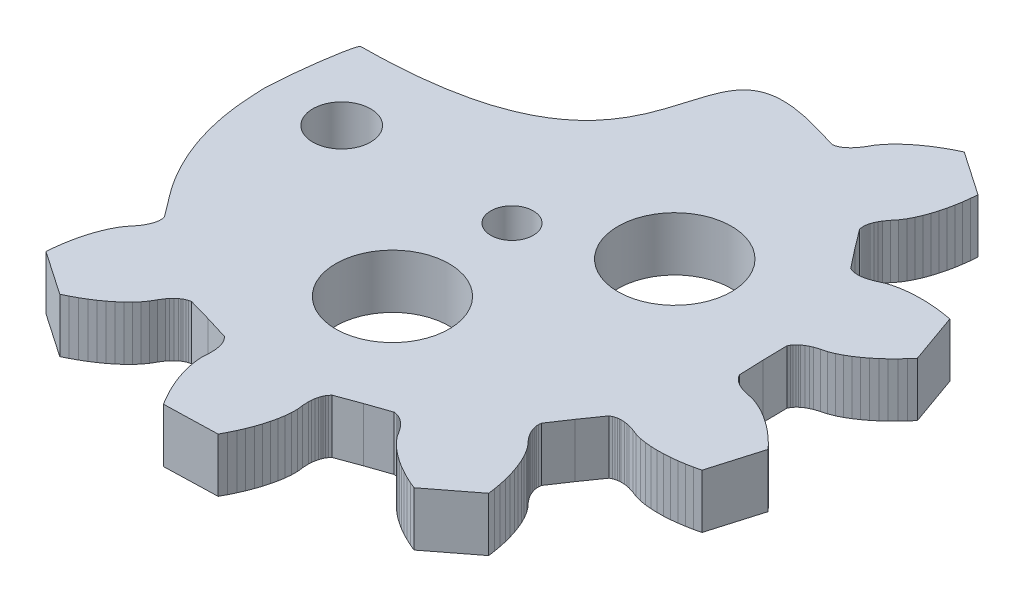
SolidWorks part; units mm, degrees
material "Acrylic (Medium-high impact)"
ref_plane "Front Plane" through (0, 0, 0) normal (0, 0, 1) x (1, 0, 0)
ref_plane "Top Plane" through (0, 0, 0) normal (0, 1, 0) x (1, 0, 0)
ref_plane "Right Plane" through (0, 0, 0) normal (1, 0, 0) x (0, 0, -1)
sketch "Sketch1" plane through (0, 0, 0) normal (0, 1, 0) x (1, 0, 0)
  line L0 (11.9142, 1.6747) -> (11.8892, 3.1027)
  line L1 (11.8892, 3.1027) -> (11.9571, 3.2377)
  line L2 (11.9571, 3.2377) -> (12.0287, 3.3392)
  line L3 (12.0287, 3.3392) -> (12.1027, 3.4228)
  line L4 (12.1027, 3.4228) -> (12.178, 3.4943)
  line L5 (12.178, 3.4943) -> (12.2543, 3.5569)
  line L6 (12.2543, 3.5569) -> (12.4097, 3.6629)
  line L7 (12.4097, 3.6629) -> (12.5679, 3.7494)
  line L8 (12.5679, 3.7494) -> (12.7284, 3.8207)
  line L9 (12.7284, 3.8207) -> (13.0552, 3.9285)
  line L10 (13.0552, 3.9285) -> (13.3853, 4.0135)
  line L11 (13.3853, 4.0135) -> (13.7083, 4.1412)
  line L12 (13.7083, 4.1412) -> (14.0252, 4.3001)
  line L13 (14.0252, 4.3001) -> (14.3366, 4.4845)
  line L14 (14.3366, 4.4845) -> (14.6428, 4.6909)
  line L15 (14.6428, 4.6909) -> (14.9436, 4.9174)
  line L16 (14.9436, 4.9174) -> (15.2386, 5.1626)
  line L17 (15.2386, 5.1626) -> (15.5281, 5.426)
  line L18 (15.5281, 5.426) -> (15.8112, 5.706)
  line L19 (15.8112, 5.706) -> (16.088, 6.0029)
  line L20 (16.088, 6.0029) -> (16.3578, 6.3157)
  line L21 (16.3578, 6.3157) -> (15.309, 9.2686)
  line L22 (15.309, 9.2686) -> (14.9028, 9.3403)
  line L23 (14.9028, 9.3403) -> (14.5009, 9.3953)
  line L24 (14.5009, 9.3953) -> (14.1048, 9.4334)
  line L25 (14.1048, 9.4334) -> (13.7145, 9.4544)
  line L26 (13.7145, 9.4544) -> (13.3309, 9.4577)
  line L27 (13.3309, 9.4577) -> (12.955, 9.4427)
  line L28 (12.955, 9.4427) -> (12.5874, 9.4089)
  line L29 (12.5874, 9.4089) -> (12.2297, 9.3549)
  line L30 (12.2297, 9.3549) -> (11.8837, 9.2777)
  line L31 (11.8837, 9.2777) -> (11.5532, 9.1725)
  line L32 (11.5532, 9.1725) -> (11.2433, 9.0291)
  line L33 (11.2433, 9.0291) -> (10.9222, 8.9061)
  line L34 (10.9222, 8.9061) -> (10.7526, 8.8599)
  line L35 (10.7526, 8.8599) -> (10.5756, 8.8267)
  line L36 (10.5756, 8.8267) -> (10.3884, 8.8106)
  line L37 (10.3884, 8.8106) -> (10.2896, 8.8108)
  line L38 (10.2896, 8.8108) -> (10.1862, 8.8187)
  line L39 (10.1862, 8.8187) -> (10.0763, 8.8369)
  line L40 (10.0763, 8.8369) -> (9.9566, 8.87)
  line L41 (9.9566, 8.87) -> (9.8189, 8.9315)
  line L42 (9.8189, 8.9315) -> (8.9378, 10.0544)
  line L43 (8.9378, 10.0544) -> (8.0794, 11.1952)
  line L44 (8.0794, 11.1952) -> (8.0555, 11.3447)
  line L45 (8.0555, 11.3447) -> (8.0538, 11.4689)
  line L46 (8.0538, 11.4689) -> (8.0647, 11.5799)
  line L47 (8.0647, 11.5799) -> (8.0835, 11.6819)
  line L48 (8.0835, 11.6819) -> (8.1087, 11.7778)
  line L49 (8.1087, 11.7778) -> (8.172, 11.9549)
  line L50 (8.172, 11.9549) -> (8.2494, 12.1181)
  line L51 (8.2494, 12.1181) -> (8.3373, 12.2702)
  line L52 (8.3373, 12.2702) -> (8.5385, 12.5499)
  line L53 (8.5385, 12.5499) -> (8.7557, 12.8132)
  line L54 (8.7557, 12.8132) -> (8.9422, 13.1067)
  line L55 (8.9422, 13.1067) -> (9.1051, 13.4219)
  line L56 (9.1051, 13.4219) -> (9.2488, 13.7543)
  line L57 (9.2488, 13.7543) -> (9.3754, 14.1016)
  line L58 (9.3754, 14.1016) -> (9.4859, 14.4619)
  line L59 (9.4859, 14.4619) -> (9.5808, 14.8343)
  line L60 (9.5808, 14.8343) -> (9.6607, 15.2176)
  line L61 (9.6607, 15.2176) -> (9.7252, 15.611)
  line L62 (9.7252, 15.611) -> (9.7749, 16.0141)
  line L63 (9.7749, 16.0141) -> (9.8097, 16.4261)
  line L64 (9.8097, 16.4261) -> (7.2288, 18.1974)
  line L65 (7.2288, 18.1974) -> (6.8578, 18.0162)
  line L66 (6.8578, 18.0162) -> (6.5006, 17.8239)
  line L67 (6.5006, 17.8239) -> (6.1577, 17.6216)
  line L68 (6.1577, 17.6216) -> (5.8298, 17.4085)
  line L69 (5.8298, 17.4085) -> (5.5176, 17.1856)
  line L70 (5.5176, 17.1856) -> (5.2218, 16.9521)
  line L71 (5.2218, 16.9521) -> (4.9445, 16.7084)
  line L72 (4.9445, 16.7084) -> (4.687, 16.4539)
  line L73 (4.687, 16.4539) -> (4.4523, 16.1878)
  line L74 (4.4523, 16.1878) -> (4.2463, 15.9079)
  line L75 (4.2463, 15.9079) -> (4.0801, 15.6096)
  line L76 (4.0801, 15.6096) -> (3.8924, 15.321)
  line L77 (3.8924, 15.321) -> (3.7825, 15.1837)
  line L78 (3.7825, 15.1837) -> (3.6587, 15.0526)
  line L79 (3.6587, 15.0526) -> (3.5164, 14.9292)
  line L80 (3.5164, 14.9292) -> (3.4364, 14.8713)
  line L81 (3.4364, 14.8713) -> (3.3483, 14.8168)
  line L82 (3.3483, 14.8168) -> (3.2487, 14.7667)
  line L83 (3.2487, 14.7667) -> (3.1326, 14.723)
  line L84 (3.1326, 14.723) -> (2.985, 14.6917)
  line L85 (2.985, 14.6917) -> (1.613, 15.0815)
  line L86 (-16.6074, 0.877) -> (-16.5676, 0.1296)
  line L87 (-13.8302, -7.5022) -> (-12.9719, -8.643)
  line L88 (-12.9719, -8.643) -> (-12.9479, -8.7922)
  line L89 (-12.9479, -8.7922) -> (-12.9465, -8.9167)
  line L90 (-12.9465, -8.9167) -> (-12.9569, -9.0275)
  line L91 (-12.9569, -9.0275) -> (-12.9761, -9.1297)
  line L92 (-12.9761, -9.1297) -> (-13.0011, -9.2256)
  line L93 (-13.0011, -9.2256) -> (-13.0644, -9.4027)
  line L94 (-13.0644, -9.4027) -> (-13.142, -9.5659)
  line L95 (-13.142, -9.5659) -> (-13.2299, -9.7181)
  line L96 (-13.2299, -9.7181) -> (-13.4307, -9.9976)
  line L97 (-13.4307, -9.9976) -> (-13.6482, -10.261)
  line L98 (-13.6482, -10.261) -> (-13.8344, -10.5542)
  line L99 (-13.8344, -10.5542) -> (-13.9973, -10.8696)
  line L100 (-13.9973, -10.8696) -> (-14.1413, -11.2021)
  line L101 (-14.1413, -11.2021) -> (-14.2679, -11.5492)
  line L102 (-14.2679, -11.5492) -> (-14.3783, -11.9097)
  line L103 (-14.3783, -11.9097) -> (-14.4732, -12.2819)
  line L104 (-14.4732, -12.2819) -> (-14.5529, -12.6652)
  line L105 (-14.5529, -12.6652) -> (-14.6176, -13.0588)
  line L106 (-14.6176, -13.0588) -> (-14.6672, -13.4619)
  line L107 (-14.6672, -13.4619) -> (-14.7023, -13.8739)
  line L108 (-14.7023, -13.8739) -> (-12.1212, -15.6451)
  line L109 (-12.1212, -15.6451) -> (-11.7503, -15.4638)
  line L110 (-11.7503, -15.4638) -> (-11.3931, -15.2717)
  line L111 (-11.3931, -15.2717) -> (-11.0502, -15.0692)
  line L112 (-11.0502, -15.0692) -> (-10.7222, -14.8565)
  line L113 (-10.7222, -14.8565) -> (-10.4098, -14.6334)
  line L114 (-10.4098, -14.6334) -> (-10.1144, -14.3999)
  line L115 (-10.1144, -14.3999) -> (-9.8369, -14.1562)
  line L116 (-9.8369, -14.1562) -> (-9.5795, -13.9017)
  line L117 (-9.5795, -13.9017) -> (-9.3446, -13.6358)
  line L118 (-9.3446, -13.6358) -> (-9.139, -13.3554)
  line L119 (-9.139, -13.3554) -> (-8.9723, -13.0574)
  line L120 (-8.9723, -13.0574) -> (-8.7848, -12.7688)
  line L121 (-8.7848, -12.7688) -> (-8.675, -12.6315)
  line L122 (-8.675, -12.6315) -> (-8.5509, -12.5004)
  line L123 (-8.5509, -12.5004) -> (-8.4091, -12.377)
  line L124 (-8.4091, -12.377) -> (-8.3288, -12.3191)
  line L125 (-8.3288, -12.3191) -> (-8.2405, -12.2645)
  line L126 (-8.2405, -12.2645) -> (-8.1412, -12.2144)
  line L127 (-8.1412, -12.2144) -> (-8.0248, -12.171)
  line L128 (-8.0248, -12.171) -> (-7.8775, -12.1395)
  line L129 (-7.8775, -12.1395) -> (-6.5055, -12.5291)
  line L130 (-6.5055, -12.5291) -> (-5.1418, -12.9469)
  line L131 (-5.1418, -12.9469) -> (-5.0349, -13.0532)
  line L132 (-5.0349, -13.0532) -> (-4.9606, -13.1529)
  line L133 (-4.9606, -13.1529) -> (-4.9041, -13.249)
  line L134 (-4.9041, -13.249) -> (-4.8595, -13.3429)
  line L135 (-4.8595, -13.3429) -> (-4.8235, -13.4352)
  line L136 (-4.8235, -13.4352) -> (-4.7711, -13.6158)
  line L137 (-4.7711, -13.6158) -> (-4.738, -13.7934)
  line L138 (-4.738, -13.7934) -> (-4.7199, -13.9683)
  line L139 (-4.7199, -13.9683) -> (-4.7185, -14.3127)
  line L140 (-4.7185, -14.3127) -> (-4.7399, -14.6538)
  line L141 (-4.7399, -14.6538) -> (-4.7185, -15.0007)
  line L142 (-4.7185, -15.0007) -> (-4.6653, -15.3519)
  line L143 (-4.6653, -15.3519) -> (-4.5866, -15.7055)
  line L144 (-4.5866, -15.7055) -> (-4.4852, -16.061)
  line L145 (-4.4852, -16.061) -> (-4.3632, -16.4176)
  line L146 (-4.3632, -16.4176) -> (-4.2216, -16.7748)
  line L147 (-4.2216, -16.7748) -> (-4.0611, -17.1319)
  line L148 (-4.0611, -17.1319) -> (-3.8825, -17.4883)
  line L149 (-3.8825, -17.4883) -> (-3.6862, -17.8435)
  line L150 (-3.6862, -17.8435) -> (-3.4727, -18.1974)
  line L151 (-3.4727, -18.1974) -> (-0.3453, -18.1106)
  line L152 (-0.3453, -18.1106) -> (-0.1518, -17.7456)
  line L153 (-0.1518, -17.7456) -> (0.0246, -17.3799)
  line L154 (0.0246, -17.3799) -> (0.1832, -17.014)
  line L155 (0.1832, -17.014) -> (0.3237, -16.6486)
  line L156 (0.3237, -16.6486) -> (0.4455, -16.2843)
  line L157 (0.4455, -16.2843) -> (0.5477, -15.9214)
  line L158 (0.5477, -15.9214) -> (0.629, -15.5609)
  line L159 (0.629, -15.5609) -> (0.6882, -15.2033)
  line L160 (0.6882, -15.2033) -> (0.7218, -14.8499)
  line L161 (0.7218, -14.8499) -> (0.7241, -14.5021)
  line L162 (0.7241, -14.5021) -> (0.6838, -14.1628)
  line L163 (0.6838, -14.1628) -> (0.6662, -13.819)
  line L164 (0.6662, -13.819) -> (0.6747, -13.6431)
  line L165 (0.6747, -13.6431) -> (0.6979, -13.4641)
  line L166 (0.6979, -13.4641) -> (0.7402, -13.2805)
  line L167 (0.7402, -13.2805) -> (0.7713, -13.1866)
  line L168 (0.7713, -13.1866) -> (0.8106, -13.0905)
  line L169 (0.8106, -13.0905) -> (0.8616, -12.9913)
  line L170 (0.8616, -12.9913) -> (0.9301, -12.8877)
  line L171 (0.9301, -12.8877) -> (1.0311, -12.7755)
  line L172 (1.0311, -12.7755) -> (2.3696, -12.2831)
  line L173 (2.3696, -12.2831) -> (3.7178, -11.8178)
  line L174 (3.7178, -11.8178) -> (3.8668, -11.841)
  line L175 (3.8668, -11.841) -> (3.9853, -11.8778)
  line L176 (3.9853, -11.8778) -> (4.0875, -11.9225)
  line L177 (4.0875, -11.9225) -> (4.1786, -11.9721)
  line L178 (4.1786, -11.9721) -> (4.2619, -12.0254)
  line L179 (4.2619, -12.0254) -> (4.4105, -12.1408)
  line L180 (4.4105, -12.1408) -> (4.5412, -12.2649)
  line L181 (4.5412, -12.2649) -> (4.6586, -12.3958)
  line L182 (4.6586, -12.3958) -> (4.862, -12.6735)
  line L183 (4.862, -12.6735) -> (5.0446, -12.9618)
  line L184 (5.0446, -12.9618) -> (5.2655, -13.2303)
  line L185 (5.2655, -13.2303) -> (5.5145, -13.4829)
  line L186 (5.5145, -13.4829) -> (5.7858, -13.7226)
  line L187 (5.7858, -13.7226) -> (6.0763, -13.9506)
  line L188 (6.0763, -13.9506) -> (6.3844, -14.1673)
  line L189 (6.3844, -14.1673) -> (6.7085, -14.3727)
  line L190 (6.7085, -14.3727) -> (7.0477, -14.5671)
  line L191 (7.0477, -14.5671) -> (7.4013, -14.7503)
  line L192 (7.4013, -14.7503) -> (7.7684, -14.9224)
  line L193 (7.7684, -14.9224) -> (8.1488, -15.0827)
  line L194 (8.1488, -15.0827) -> (10.6279, -13.1711)
  line L195 (10.6279, -13.1711) -> (10.5704, -12.7615)
  line L196 (10.5704, -12.7615) -> (10.4985, -12.3619)
  line L197 (10.4985, -12.3619) -> (10.4123, -11.9725)
  line L198 (10.4123, -11.9725) -> (10.3116, -11.5942)
  line L199 (10.3116, -11.5942) -> (10.1961, -11.2277)
  line L200 (10.1961, -11.2277) -> (10.0659, -10.8741)
  line L201 (10.0659, -10.8741) -> (9.9203, -10.5342)
  line L202 (9.9203, -10.5342) -> (9.7585, -10.2105)
  line L203 (9.7585, -10.2105) -> (9.5782, -9.9046)
  line L204 (9.5782, -9.9046) -> (9.376, -9.622)
  line L205 (9.376, -9.622) -> (9.1444, -9.3712)
  line L206 (9.1444, -9.3712) -> (8.9281, -9.1032)
  line L207 (8.9281, -9.1032) -> (8.832, -8.9562)
  line L208 (8.832, -8.9562) -> (8.7459, -8.7977)
  line L209 (8.7459, -8.7977) -> (8.6725, -8.6242)
  line L210 (8.6725, -8.6242) -> (8.6422, -8.5299)
  line L211 (8.6422, -8.5299) -> (8.6179, -8.4291)
  line L212 (8.6179, -8.4291) -> (8.6009, -8.3186)
  line L213 (8.6009, -8.3186) -> (8.5955, -8.1947)
  line L214 (8.5955, -8.1947) -> (8.6115, -8.0444)
  line L215 (8.6115, -8.0444) -> (9.4053, -6.8576)
  line L216 (9.4053, -6.8576) -> (10.2231, -5.6875)
  line L217 (10.2231, -5.6875) -> (10.3574, -5.6184)
  line L218 (10.3574, -5.6184) -> (10.4746, -5.5786)
  line L219 (10.4746, -5.5786) -> (10.5835, -5.5544)
  line L220 (10.5835, -5.5544) -> (10.6863, -5.5409)
  line L221 (10.6863, -5.5409) -> (10.7849, -5.5352)
  line L222 (10.7849, -5.5352) -> (10.9728, -5.5409)
  line L223 (10.9728, -5.5409) -> (11.1516, -5.5641)
  line L224 (11.1516, -5.5641) -> (11.3233, -5.601)
  line L225 (11.3233, -5.601) -> (11.6507, -5.706)
  line L226 (11.6507, -5.706) -> (11.968, -5.8317)
  line L227 (11.968, -5.8317) -> (12.3041, -5.9187)
  line L228 (12.3041, -5.9187) -> (12.6538, -5.9762)
  line L229 (12.6538, -5.9762) -> (13.0138, -6.0108)
  line L230 (13.0138, -6.0108) -> (13.3825, -6.0241)
  line L231 (13.3825, -6.0241) -> (13.7587, -6.0181)
  line L232 (13.7587, -6.0181) -> (14.1415, -5.9934)
  line L233 (14.1415, -5.9934) -> (14.5301, -5.9508)
  line L234 (14.5301, -5.9508) -> (14.9238, -5.8908)
  line L235 (14.9238, -5.8908) -> (15.3217, -5.8137)
  line L236 (15.3217, -5.8137) -> (15.7235, -5.7196)
  line L237 (15.7235, -5.7196) -> (16.6074, -2.713)
  line L238 (16.6074, -2.713) -> (16.3208, -2.4159)
  line L239 (16.3208, -2.4159) -> (16.0281, -2.1348)
  line L240 (16.0281, -2.1348) -> (15.73, -1.8704)
  line L241 (15.73, -1.8704) -> (15.4264, -1.6239)
  line L242 (15.4264, -1.6239) -> (15.118, -1.3953)
  line L243 (15.118, -1.3953) -> (14.8051, -1.1859)
  line L244 (14.8051, -1.1859) -> (14.488, -0.9968)
  line L245 (14.488, -0.9968) -> (14.1671, -0.83)
  line L246 (14.1671, -0.83) -> (13.8417, -0.6887)
  line L247 (13.8417, -0.6887) -> (13.5123, -0.5792)
  line L248 (13.5123, -0.5792) -> (13.1779, -0.5126)
  line L249 (13.1779, -0.5126) -> (12.8459, -0.4231)
  line L250 (12.8459, -0.4231) -> (12.6816, -0.3609)
  line L251 (12.6816, -0.3609) -> (12.5187, -0.2832)
  line L252 (12.5187, -0.2832) -> (12.3579, -0.186)
  line L253 (12.3579, -0.186) -> (12.278, -0.1276)
  line L254 (12.278, -0.1276) -> (12.199, -0.0604)
  line L255 (12.199, -0.0604) -> (12.1206, 0.019)
  line L256 (12.1206, 0.019) -> (12.0434, 0.1163)
  line L257 (12.0434, 0.1163) -> (11.968, 0.247)
  line L258 (11.968, 0.247) -> (11.9142, 1.6747)
  line L259 (-14.128, 1.2082) -> (-10.7287, 1.2761) construction
  line L260 (-2.4462, 2.5262) -> (-2.4462, 0.0262) construction
  line L261 (2.7597, 7.2598) -> (5.5764, 1.2085) construction
  line L262 (-5.5629, -6.0825) -> (1.0996, -5.8575) construction
  circle A0 centre (-12.4283, 1.2422) radius 1.7
  circle A1 centre (-2.2316, -5.97) radius 3.3331
  circle A2 centre (-2.4462, 1.2762) radius 1.25
  circle A3 centre (4.168, 4.2341) radius 3.3374
  spline S0 degree 3 poles (1.613, 15.0815) (-7.7297, 17.7862) (2.3339, 5.8981) (-15.8908, 5.8248) knots 86 86 86 86 87 87 87 87
  spline S1 degree 3 poles (-15.8908, 5.8248) (-16.088, 5.804) (-16.5321, 2.8034) (-16.6074, 0.877) knots 87 87 87 87 88 88 88 88
  spline S2 degree 3 poles (-16.5676, 0.1296) (-16.408, -3.8216) (-14.671, -6.4292) (-13.8302, -7.5022) knots 89 89 89 89 90 90 90 90
  dimension "D1" = 3.4
  dimension "D2" = 2.5
extrude "Boss-Extrude1" add sketch "Sketch1" along normal blind 3.175
